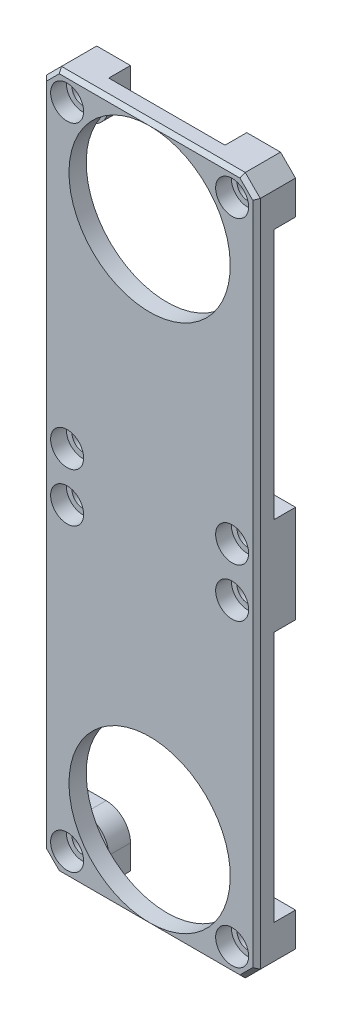
SolidWorks part; units mm, degrees
ref_plane "Front Plane" through (0, 0, 0) normal (0, 0, 1) x (1, 0, 0)
ref_plane "Top Plane" through (0, 0, 0) normal (0, 1, 0) x (1, 0, 0)
ref_plane "Right Plane" through (0, 0, 0) normal (1, 0, 0) x (0, 0, -1)
sketch "Sketch2" plane through (0, 0, 0) normal (0, 0, 1) x (1, 0, 0)
  line L0 (0, 0) -> (0, -50000) construction
  line L1 (-14.25, 11.25) -> (14.25, 11.25)
  line L2 (-14.25, 11.25) -> (-14.25, -81.75)
  line L5 (-14.25, -35.25) -> (32.3629, -35.25) construction
  line L6 (14.25, 11.25) -> (14.25, -81.75)
  line L7 (-14.25, -81.75) -> (14.25, -81.75)
  line L8 (-7.75, 11.25) -> (-7.75, 8) construction
  line L9 (-11, 4.75) -> (-14.25, 4.75) construction
  line L10 (-13.95, -12) -> (13.95, -12) construction
  arc A2 (-7.75, 8) -> (-11, 4.75) centre (-11, 8) cw construction
  circle A3 centre (0, 0) radius 10.75
  circle A4 centre (0, -70.5) radius 10.75
  point P1 (-11, -32)
  point P2 (11, -38.5)
  point P3 (11, 8)
  point P12 (-11, 8)
  point P16 (0, 11.25)
  point P17 (11, -32)
  point P19 (14.25, -35.25)
  point P20 (-14.25, -35.25)
  point P21 (0, -81.75)
  point P22 (-11, -78.5)
  point P23 (11, -78.5)
  point P24 (-11, -38.5)
  dimension "D5" = 21.5
  dimension "D1" = 28.5
  dimension "D2" = 93
  dimension "D3" = 22
  dimension "D4" = 40
extrude "Boss-Extrude1" add sketch "Sketch2" along normal blind 2.3
sketch "Sketch3" plane through (0, 0, 0) normal (0, 0, -1) x (-1, 0, 0)
  line L0 (7.75, 11.25) -> (7.75, 8)
  line L1 (11, 4.75) -> (14.25, 4.75)
  line L2 (14.25, 4.75) -> (14.25, 11.25)
  line L3 (14.25, 11.25) -> (7.75, 11.25)
  line L4 (-13.95, -12) -> (13.95, -12) construction
  line L5 (0, -31.367) -> (0, -2.7168) construction
  line L6 (11, -41.75) -> (14.25, -41.75)
  line L8 (14.25, -28.75) -> (14.25, -41.75)
  line L9 (11, -28.75) -> (14.25, -28.75)
  line L10 (7.75, -38.5) -> (7.75, -32)
  line L11 (-14.25, -35.25) -> (14.25, -35.25) construction
  line L12 (14.25, -81.75) -> (7.75, -81.75)
  line L13 (14.25, -75.25) -> (14.25, -81.75)
  line L14 (11, -75.25) -> (14.25, -75.25)
  line L15 (7.75, -81.75) -> (7.75, -78.5)
  line L16 (-14.25, 11.25) -> (-7.75, 11.25)
  line L17 (-14.25, 4.75) -> (-14.25, 11.25)
  line L18 (-11, 4.75) -> (-14.25, 4.75)
  line L19 (-7.75, 11.25) -> (-7.75, 8)
  line L20 (-7.75, -38.5) -> (-7.75, -32)
  line L21 (-11, -28.75) -> (-14.25, -28.75)
  line L22 (-14.25, -28.75) -> (-14.25, -41.75)
  line L23 (-11, -41.75) -> (-14.25, -41.75)
  line L24 (-7.75, -81.75) -> (-7.75, -78.5)
  line L25 (-11, -75.25) -> (-14.25, -75.25)
  line L26 (-14.25, -75.25) -> (-14.25, -81.75)
  line L27 (-14.25, -81.75) -> (-7.75, -81.75)
  arc A0 (7.75, 8) -> (11, 4.75) centre (11, 8) ccw
  arc A1 (7.75, -32) -> (11, -28.75) centre (11, -32) cw
  arc A2 (7.75, -38.5) -> (11, -41.75) centre (11, -38.5) ccw
  arc A3 (7.75, -78.5) -> (11, -75.25) centre (11, -78.5) cw
  arc A4 (-7.75, 8) -> (-11, 4.75) centre (-11, 8) cw
  arc A5 (-7.75, -38.5) -> (-11, -41.75) centre (-11, -38.5) cw
  arc A6 (-7.75, -32) -> (-11, -28.75) centre (-11, -32) ccw
  arc A7 (-7.75, -78.5) -> (-11, -75.25) centre (-11, -78.5) ccw
  point P31 (7.75, -35.25)
  point P32 (14.25, -35.25)
  point P49 (-14.25, -35.25)
  point P50 (-7.75, -35.25)
extrude "Boss-Extrude2" add sketch "Sketch3" along normal blind 2.9
sketch "Sketch7" plane through (0, 0, 2.3) normal (0, 0, 1) x (1, 0, 0)
  point P0 (-11, 8)
  point P1 (11, 8)
  point P3 (11, -32)
  point P5 (-11, -32)
  point P7 (-11, -38.5)
  point P9 (11, -38.5)
  point P11 (11, -78.5)
  point P13 (-11, -78.5)
hole_wizard "CBORE for M2.5 Pan Head Screw1" positions "Sketch8" profile "Sketch9" counterbore size "M2.5" standard "ISO"
sketch "Sketch8" plane through (0, 0, 2.3) normal (0, 0, 1) x (1, 0, 0)
  point P0 (-11, 8)
  point P3 (11, 8)
  point P6 (11, -32)
  point P9 (-11, -32)
  point P12 (-11, -38.5)
  point P15 (11, -38.5)
  point P18 (11, -78.5)
  point P21 (-11, -78.5)
sketch "Sketch9" plane through (-11, 8, 2.3) normal (1, 0, 0) x (0, -1, 0)
  line L0 (0, 0) -> (0, 8.8712)
  line L1 (0, 8.8712) -> (1.45, 8)
  line L2 (1.45, 8) -> (1.45, 2.1)
  line L3 (1.45, 2.1) -> (2.2, 2.1)
  line L4 (2.2, 2.1) -> (2.2, 0)
  line L5 (2.2, 0) -> (0, 0)
  line L10 (0, 8.8712) -> (-1.45, 8) construction
  line L11 (0, -6.35) -> (0, 107.95) construction
  dimension "Hole Dia." = 2.9
  dimension "Hole Depth" = 8
  dimension "C'Bore Dia." = 4.4
  dimension "C'Bore Depth" = 2.1
  dimension "Drill Angle" = 118
chamfer "Chamfer1" distance 2 angle 45 4 edges at (-14.25, -81.75, -0.3) (14.25, -81.75, -0.3) (14.25, 11.25, -0.3) (-14.25, 11.25, -0.3)
chamfer "Chamfer2" distance 0.5 angle 45 8 edges at (-13.25, 10.25, 2.3) (0, 11.25, 2.3) (13.25, 10.25, 2.3) (14.25, -35.25, 2.3) (13.25, -80.75, 2.3) (0, -81.75, 2.3) (-13.25, -80.75, 2.3) (-14.25, -35.25, 2.3)
